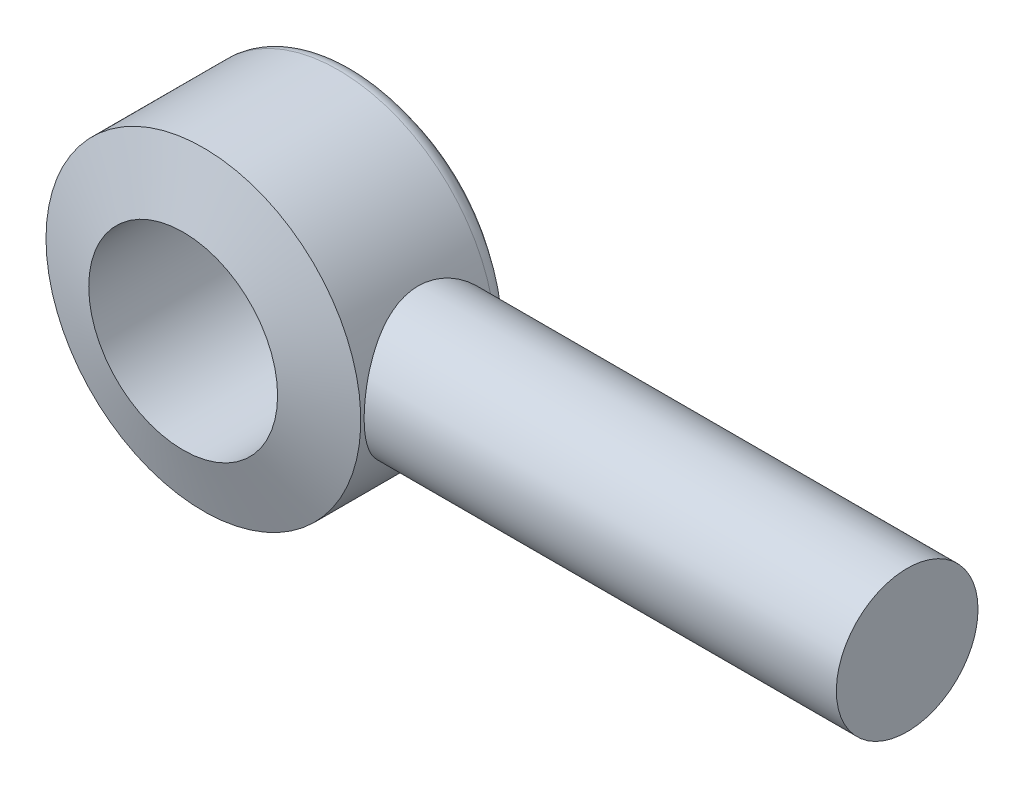
SolidWorks part; units mm, degrees
ref_plane "Front Plane" through (0, 0, 0) normal (0, 0, 1) x (1, 0, 0)
ref_plane "Top Plane" through (0, 0, 0) normal (0, 1, 0) x (1, 0, 0)
ref_plane "Right Plane" through (0, 0, 0) normal (1, 0, 0) x (0, 0, -1)
sketch "Sketch2" plane through (0, 0, 0) normal (0, 1, 0) x (1, 0, 0)
  line L0 (0, 10) -> (0, -12) construction
  line L1 (0, -12) -> (20, -12) construction
  line L2 (20, -12) -> (20, 7.7088)
  line L3 (19.2189, 9.2944) -> (17.539, 10.5857)
  line L4 (16.3202, 11) -> (12, 11)
  line L5 (0, 10) -> (12, 10)
  line L6 (12, 10) -> (12, 11)
  line L7 (12, -12) -> (12, 7.4973)
  line L8 (12, 7.4973) -> (0, 7.4973)
  line L9 (12, -12) -> (20, -12)
  line L10 (0, 10) -> (0, 7.4973)
  line L11 (0, 10) -> (0, 7.4973)
  line L12 (12, -12) -> (20, -9.4302)
  arc A0 (20, 7.7088) -> (19.2189, 9.2944) centre (18, 7.7088) ccw
  arc A1 (17.539, 10.5857) -> (16.3202, 11) centre (16.3202, 9) ccw
  point P15 (17, 11)
  dimension "D7" = 2
  dimension "D1" = 10
  dimension "D2" = 12
  dimension "D3" = 20
  dimension "D4" = 12
  dimension "D5" = 5
  dimension "D6" = 1
revolve "Revolve1" add sketch "Sketch2" angle 360 about L0 region at (14.3759, 0, -1.2401)
sketch3d "3DSketch1"
  line L0 (0, 0, 0) -> (80, 0, 0) construction
  circle A0 centre (80, 0, 0) radius 9
  circle A1 centre (80, 0, 0) radius 9
  point P4 (89, 0, 0)
  point P6 (71, 0, 0)
  dimension "D2" = 18
  dimension "D1" = 80
extrude "Boss-Extrude3" add sketch "3DSketch1" along direction (1, 0, 0) on the side against the normal blind 65 contours A0
